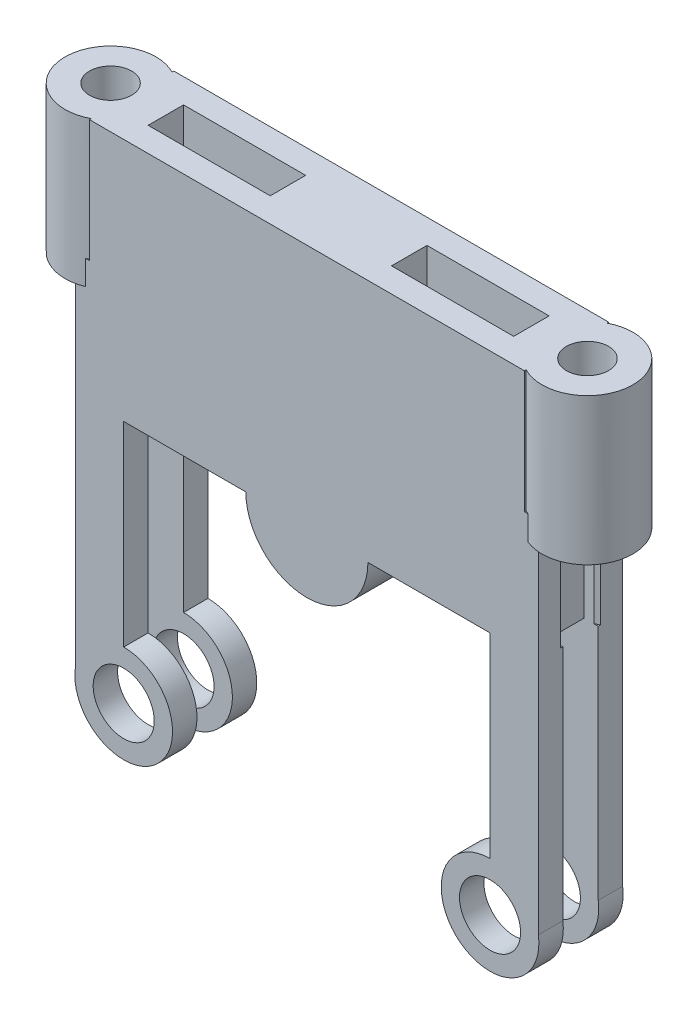
SolidWorks part; units mm, degrees
note: The reader was unsure of these and kept them because the rebuilt part matched: shared geometry of "Sketch2<3>".
ref_plane "Front Plane" through (0, 0, 0) normal (0, 0, 1) x (1, 0, 0)
ref_plane "Top Plane" through (0, 0, 0) normal (0, 1, 0) x (1, 0, 0)
ref_plane "Right Plane" through (0, 0, 0) normal (1, 0, 0) x (0, 0, -1)
sketch "Sketch1" plane through (0, 0, 0) normal (0, 1, 0) x (1, 0, 0)
  line L2 (10.033, -0.9207) -> (10.033, 0.9208)
  line L4 (-10.033, -0.9208) -> (-10.033, 0.9207)
  line L10 (11.3047, 2.1907) -> (-11.3047, 2.1907)
  line L11 (2.6257, 0.9208) -> (2.6257, -0.9207)
  line L12 (11.3047, 2.1907) -> (11.3047, -2.1907)
  line L13 (11.3047, -2.1907) -> (-11.3047, -2.1907)
  line L14 (-11.3047, 2.1907) -> (-11.3047, -2.1907)
  line L15 (11.3047, 2.1907) -> (-11.3047, -2.1907) construction
  line L16 (11.3047, -2.1907) -> (-11.3047, 2.1907) construction
  line L28 (-2.667, 0.9208) -> (-2.667, -0.9207)
  line L30 (-10.033, 0.9207) -> (-2.667, 0.9208)
  line L31 (-10.033, 0.9207) -> (-10.033, -0.9208)
  line L32 (-10.033, -0.9208) -> (-2.667, -0.9207)
  line L33 (-2.667, 0.9208) -> (-2.667, -0.9207)
  line L34 (2.6257, 0.9208) -> (10.033, 0.9208)
  line L35 (2.6257, 0.9208) -> (2.6257, -0.9207)
  line L36 (2.6257, -0.9207) -> (10.033, -0.9207)
  line L37 (10.033, 0.9208) -> (10.033, -0.9207)
  point P0 (0, 0)
  point P6 (0, 0)
  point P7 (0, 0)
  point P8 (0, 0)
  point P14 (0, 0)
  dimension "D1" = 1.8415
  dimension "D2" = 20.066
  dimension "D7" = 4.3815
extrude "Boss-Extrude1" add sketch "Sketch1" along normal blind 6.35
ref_plane "Plane1" through (0, 0, 0) normal (0, 0, 1) x (1, 0, 0)
sketch "Sketch2" plane through (0, 0, 0) normal (0, 0, 1) x (1, 0, 0)
  line L0 (3.175, 0) -> (-3.175, 0)
  line L1 (11.3047, 0) -> (-11.3047, 0) construction
  arc A0 (-3.175, 0) -> (3.175, 0) centre (0, 0) ccw
  point P6 (0, 0)
  dimension "D1" = 6.35
extrude "Boss-Extrude2" add sketch "Sketch2" against normal up to surface (2.1907 mm away) up to face at (0, 3.175, -2.1907)
extrude "Boss-Extrude3" add sketch "Sketch2<3>" along normal up to surface (2.1907 mm away) up to face at (0, 3.175, 2.1907)
sketch "Sketch2<3>" plane through (0, 0, 0) normal (0, 0, 1) x (1, 0, 0) same geometry as "Sketch2"
sketch "Sketch6" plane through (0, 0, 0) normal (0, -1, 0) x (1, 0, 0)
  line L0 (-9.525, 0.9207) -> (-11.3047, 0.9207)
  line L1 (-11.3047, -2.1907) -> (-11.3047, 2.1907) construction
  line L2 (9.4837, 0.9207) -> (11.3047, 0.9207)
  line L3 (11.3047, -2.1907) -> (11.3047, 2.1907) construction
sketch "Sketch7" plane through (0, 0, 2.1907) normal (0, 0, 1) x (1, 0, 0)
  line L6 (-9.525, 0) -> (-9.525, -10.16)
  line L7 (-11.3047, 0) -> (-9.525, 0)
  line L11 (-12.0396, 0) -> (-12.0396, -12.342)
  line L12 (-11.3047, 6.35) -> (-12.0396, 6.35)
  line L13 (-11.3047, 6.35) -> (-11.3047, 0)
  line L15 (-12.0396, 6.35) -> (-12.0396, 0)
  circle A0 centre (-9.525, -12.7) radius 1.5875
  arc A4 (-9.525, -10.16) -> (-12.0396, -12.342) centre (-9.525, -12.7) cw
  point P6 (-9.525, -10.16)
  point P11 (-7.9375, -12.7)
  point P12 (-7.9375, -12.7)
  point P13 (-9.525, -11.1125)
  point P14 (-11.3047, -10.8877)
  point P15 (-11.1125, -12.7)
extrude "Boss-Extrude4" add sketch "Sketch7" against normal blind 1.27
mirror "Mirror1" about plane through (0, 0, 0) normal (1, 0, 0) of "Boss-Extrude4"
mirror "Mirror2" about plane through (0, 0, 0) normal (0, 0, 1) of "Mirror1", "Boss-Extrude4"
sketch "Sketch8" plane through (0, 6.35, 0) normal (0, 1, 0) x (1, 0, 0)
  line L1 (0, 0) -> (0, 2.1907) construction
  line L3 (12.0396, 2.1907) -> (-12.0396, 2.1907) construction
  circle A0 centre (12.4001, 0) radius 1.0954
  circle A4 centre (-12.4001, 0) radius 2.3671
  circle A5 centre (-12.4001, 0) radius 1.0954
  circle A6 centre (12.4001, 0) radius 2.3671
extrude "Boss-Extrude5" add sketch "Sketch8" against normal blind 1.27 and the other way blind 6.35
sketch "Sketch9" plane through (0, 0, -2.1907) normal (0, 0, -1) x (-1, 0, 0)
  line L0 (11.3047, 6.35) -> (11.3047, 12.7)
  line L2 (-11.3047, 6.35) -> (11.3047, 6.35)
  line L3 (-11.3047, 6.35) -> (-11.3047, 12.7)
  line L4 (-11.3047, 12.7) -> (11.3047, 12.7)
  line L5 (11.3047, 6.35) -> (11.3047, 12.7)
  dimension "D1" = 6.35
extrude "Boss-Extrude6" add sketch "Sketch9" against normal up to surface (4.3815 mm away) contours L3 L2 L5 L4 up to face at (-7.9375, -12.7, 2.1907)
sketch "Sketch10" plane through (0, 12.7, 0) normal (0, 1, 0) x (1, 0, 0)
  line L1 (-9.525, 0.9208) -> (-3.175, 0.9208)
  line L2 (-9.525, 0.9208) -> (-9.525, -0.9207)
  line L3 (-9.525, -0.9207) -> (-3.175, -0.9207)
  line L4 (-3.175, 0.9208) -> (-3.175, -0.9207)
  line L5 (3.1337, 0.9208) -> (9.4837, 0.9208)
  line L6 (3.1337, 0.9208) -> (3.1337, -0.9207)
  line L7 (3.1337, -0.9207) -> (9.4837, -0.9207)
  line L8 (9.4837, 0.9208) -> (9.4837, -0.9207)
extrude "Cut-Extrude1" cut sketch "Sketch10" against normal up to surface (12.7 mm away) contours L8 L5 L6 L7 | L2 L1 L4 L3 up to face at (6.35, 0, -1.5558)
sketch "Sketch11" plane through (0, 12.7, 0) normal (0, 1, 0) x (1, 0, 0)
  line L0 (-11.3047, 2.1907) -> (-11.3047, -2.1907) construction
  line L1 (-11.3047, 2.1907) -> (-11.3047, -2.1907)
  line L2 (0, 0) -> (0, 2.1907) construction
  line L3 (11.3047, 2.1908) -> (11.3047, -2.1907)
  circle A0 centre (-12.4001, 0) radius 0.635
  arc A1 (-11.3047, 2.1907) -> (-11.3047, -2.1907) centre (-11.3047, 0) ccw
  arc A2 (11.3047, 2.1908) -> (11.3047, -2.1907) centre (11.3047, 0) cw
  circle A3 centre (12.4001, 0) radius 0.635
sketch "Sketch12" plane through (0, 12.7, 0) normal (0, 1, 0) x (1, 0, 0)
  circle A0 centre (-12.4001, 0) radius 1.0954
  circle A1 centre (12.4001, 0) radius 1.0954
extrude "Cut-Extrude2" cut sketch "Sketch12" against normal up to surface (12.7 mm away) up to face at (-6.35, 0, 1.5557)
